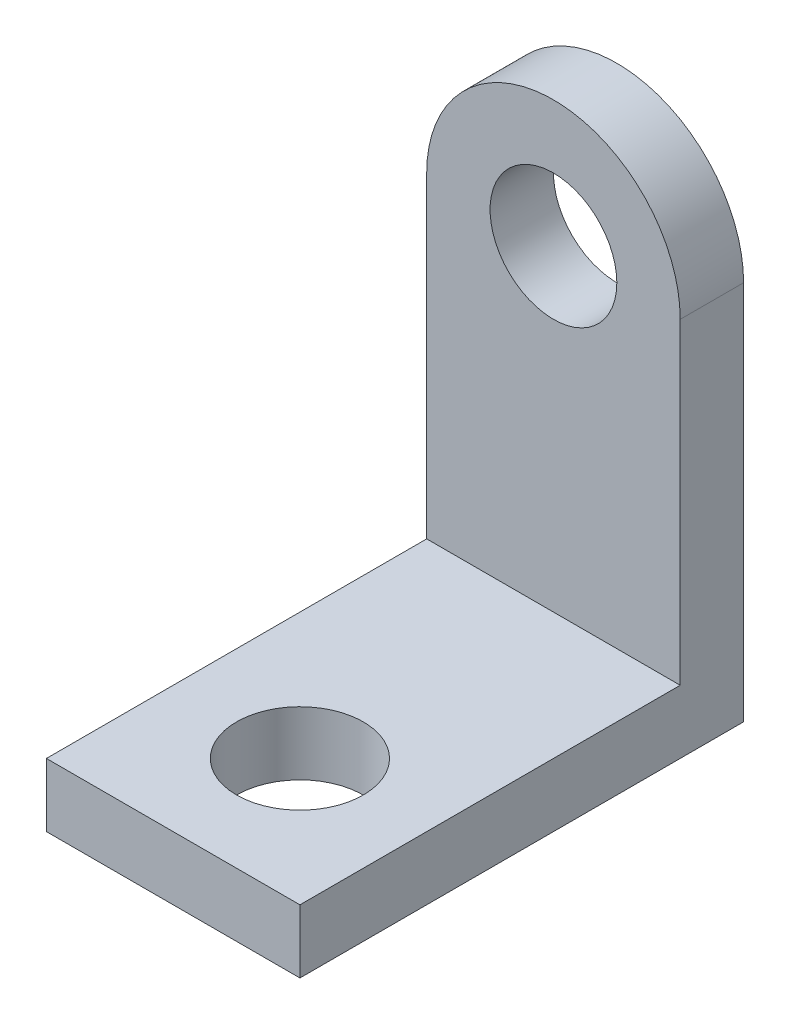
SolidWorks part; units mm, degrees
ref_plane "Front Plane" through (0, 0, 0) normal (0, 0, 1) x (1, 0, 0)
ref_plane "Top Plane" through (0, 0, 0) normal (0, 1, 0) x (1, 0, 0)
ref_plane "Right Plane" through (0, 0, 0) normal (1, 0, 0) x (0, 0, -1)
sketch "Sketch1" plane through (0, 0, 0) normal (0, 0, 1) x (1, 0, 0)
  line L0 (-6.35, 0) -> (-6.35, -19.05)
  line L1 (-6.35, -19.05) -> (6.35, -19.05)
  line L2 (6.35, -19.05) -> (6.35, 0)
  arc A0 (6.35, 0) -> (-6.35, 0) centre (0, 0) ccw
  circle A1 centre (0, 0) radius 3.175
  dimension "D1" = 12.7
  dimension "D2" = 6.35
  dimension "D3" = 19.05
extrude "Boss-Extrude1" add sketch "Sketch1" along normal blind 3.175
sketch "Sketch2" plane through (0, 0, 3.175) normal (0, 0, 1) x (1, 0, 0)
  line L0 (6.35, -19.05) -> (6.35, 0) construction
  line L1 (-6.35, -19.05) -> (6.35, -19.05)
  line L2 (-6.35, -19.05) -> (-6.35, -15.875)
  line L3 (-6.35, -15.875) -> (6.35, -15.875)
  line L4 (6.35, -19.05) -> (6.35, -15.875)
  dimension "D1" = 3.175
extrude "Boss-Extrude2" add sketch "Sketch2" along normal blind 19.05
sketch "Sketch3" plane through (0, -15.875, 0) normal (0, 1, 0) x (1, 0, 0)
  line L0 (-6.35, -22.225) -> (-6.35, -3.175) construction
  line L1 (6.35, -22.225) -> (-6.35, -22.225) construction
  circle A0 centre (0, -15.875) radius 3.175
  dimension "D1" = 6.35
  dimension "D2" = 6.35
  dimension "D3" = 6.35
extrude "Cut-Extrude1" cut sketch "Sketch3" against normal blind 19.05
